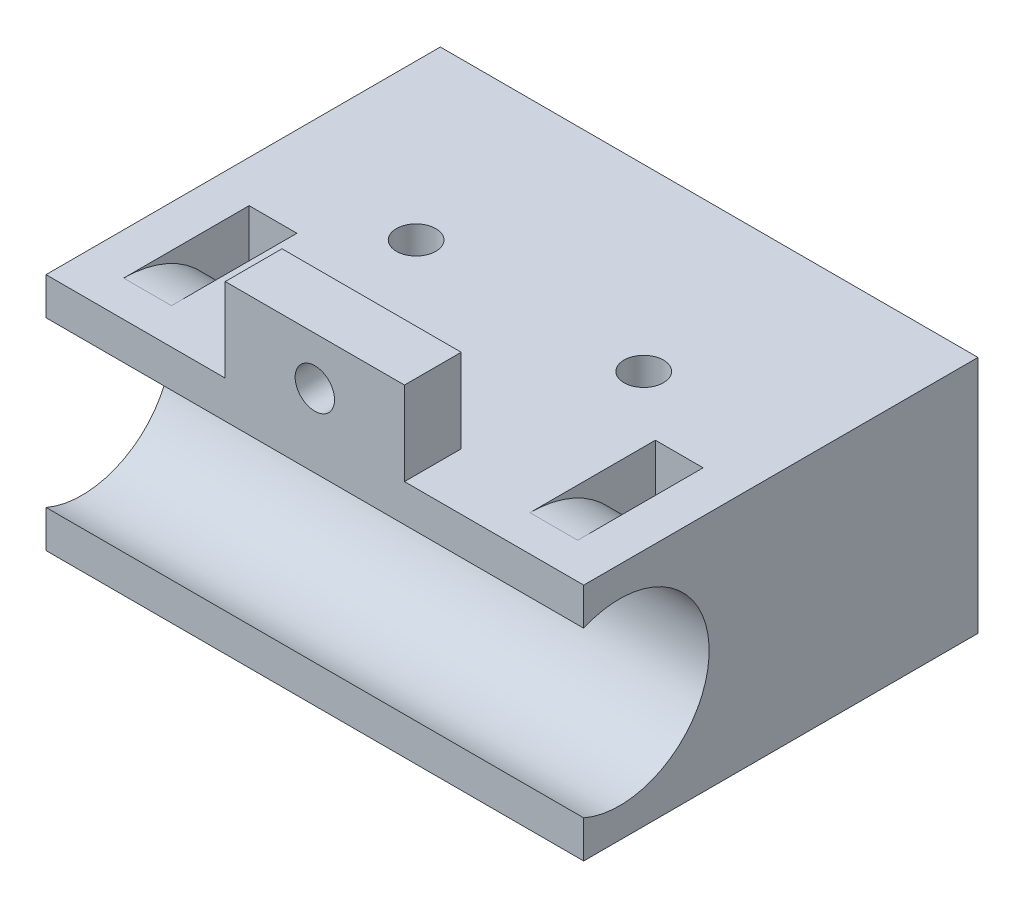
SolidWorks part; units mm, degrees
ref_plane "Front Plane" through (0, 0, 0) normal (0, 0, 1) x (1, 0, 0)
ref_plane "Top Plane" through (0, 0, 0) normal (0, 1, 0) x (1, 0, 0)
ref_plane "Right Plane" through (0, 0, 0) normal (1, 0, 0) x (0, 0, -1)
sketch "Sketch2" plane through (0, 0, 0) normal (0, 0, 1) x (1, 0, 0)
  line L1 (22.5, 10) -> (-22.5, 10)
  line L2 (22.5, 10) -> (22.5, -10)
  line L3 (22.5, -10) -> (-22.5, -10)
  line L4 (-22.5, 10) -> (-22.5, -10)
  line L5 (22.5, 10) -> (-22.5, -10) construction
  line L6 (22.5, -10) -> (-22.5, 10) construction
  point P0 (0, 0)
  dimension "D1" = 20
  dimension "D2" = 45
extrude "Boss-Extrude1" add sketch "Sketch2" along normal blind 33
hole_wizard "M4x0.7 Tapped Hole1" positions "Sketch7" profile "Sketch6" tap size "M4x0.7" standard "ANSI Metric" end condition through all
sketch "Sketch7" plane through (0, -10, 0) normal (0, -1, 0) x (-1, 0, 0)
  line L0 (0, 0) -> (0, -15) construction
  line L3 (9.525, -15) -> (-9.525, -15) construction
  point P0 (-9.525, -15)
  point P2 (9.525, -15)
  dimension "D1" = 19.05
  dimension "D2" = 15
cosmetic thread "Hole Thread1" parameters "D2"=4
cosmetic thread "Hole Thread2" parameters "D2"=4
sketch "Sketch6" plane through (9.525, -10, 15) normal (1, 0, 0) x (0, 0, -1)
  line L0 (0, 0) -> (0, 20)
  line L1 (0, 20) -> (1.65, 20)
  line L2 (1.65, 20) -> (1.65, 0)
  line L5 (1.65, 0) -> (0, 0)
  line L11 (0, -6.35) -> (0, 107.95) construction
  dimension "Thru Tap Drill Dia." = 3.3
  dimension "Thru Tap Drill Depth" = 20
sketch "Sketch3" plane through (22.5, 0, 0) normal (1, 0, 0) x (0, 0, -1)
  line L0 (-30, 0) -> (0, 0) construction
  circle A0 centre (-30, 0) radius 7.5
  dimension "D1" = 15
  dimension "D2" = 30
extrude "Cut-Extrude1" cut sketch "Sketch3" against normal blind 45
sketch "Sketch4" plane through (0, 0, 0) normal (0, 0, -1) x (-1, 0, 0)
  line L4 (22.5, -10) -> (22.5, 10)
  line L5 (22.5, 10) -> (-22.5, 10)
  line L6 (-22.5, 10) -> (-22.5, -10)
  line L7 (-22.5, -10) -> (22.5, -10)
  line L8 (22.5, -10) -> (22.5, 10)
  line L9 (22.5, 10) -> (-22.5, 10)
  line L10 (-22.5, 10) -> (-22.5, -10)
  line L11 (-22.5, -10) -> (22.5, -10)
  circle A0 centre (-15, 0) radius 4
  circle A1 centre (15, 0) radius 4
  dimension "D2" = 8
  dimension "D3" = 30
  dimension "D4" = 15
  dimension "D1" = 0
extrude "Cut-Extrude2" cut sketch "Sketch4" against normal blind 10 contours A0 | A1 region at (15, 0, 0) region at (-15, 0, 0)
hole_wizard "M3x0.5 Tapped Hole1" positions "Sketch15" profile "Sketch16" tap size "M3x0.5" standard "ANSI Metric"
sketch "Sketch15" plane through (0, 10, 0) normal (0, 1, 0) x (1, 0, 0)
  line L0 (0, 0) -> (0, -5) construction
  line L3 (-9.525, -5) -> (9.525, -5) construction
  point P0 (9.525, -5)
  point P2 (-9.525, -5)
  dimension "D1" = 19.05
  dimension "D2" = 5
sketch "Sketch16" plane through (9.525, 10, 5) normal (1, 0, 0) x (0, 0, 1)
  line L0 (0, 0) -> (0, 9.2511)
  line L1 (0, 9.2511) -> (1.25, 8.5)
  line L2 (1.25, 8.5) -> (1.25, 0)
  line L5 (1.25, 0) -> (0, 0)
  line L10 (0, 9.2511) -> (-1.25, 8.5) construction
  line L11 (0, -6.35) -> (0, 107.95) construction
  dimension "Tap Drill Dia." = 2.5
  dimension "Tap Drill Depth" = 8.5
  dimension "Drill Angle" = 118
cosmetic thread "Hole Thread7" parameters "D1"=6, "D2"=3
cosmetic thread "Hole Thread8" parameters "D1"=6, "D2"=3
sketch "Sketch5" plane through (0, -10, 0) normal (0, -1, 0) x (1, 0, 0)
  line L0 (0, 19.5) -> (0, 0) construction
  line L1 (-19, 21) -> (-15, 21)
  line L2 (-19, 21) -> (-19, 19.5)
  line L3 (-19, 19.5) -> (-15, 19.5)
  line L4 (-15, 21) -> (-15, 19.5)
  line L5 (-2, 19.5) -> (2, 19.5)
  line L6 (-2, 19.5) -> (-2, 21)
  line L7 (-2, 21) -> (2, 21)
  line L8 (2, 19.5) -> (2, 21)
  line L9 (15, 19.5) -> (19, 19.5)
  line L10 (15, 19.5) -> (15, 21)
  line L11 (15, 21) -> (19, 21)
  line L12 (19, 19.5) -> (19, 21)
  line L13 (-22.5, 19.5) -> (-19, 19.5) construction
  line L14 (-22.5, 33) -> (-22.5, 0) construction
  line L15 (-2, 19.5) -> (-15, 19.5) construction
  line L16 (2, 19.5) -> (15, 19.5) construction
  line L17 (19, 19.5) -> (22.5, 19.5) construction
  line L18 (22.5, 33) -> (22.5, 0) construction
  line L27 (-22.5, 0) -> (22.5, 0) construction
  dimension "D1" = 4
  dimension "D2" = 1.5
  dimension "D3" = 30
  dimension "D4" = 21
extrude "Cut-Extrude3" cut sketch "Sketch5" against normal blind 39 contours L4 L1 L2 L3 | L9 L12 L11 L10 region at (-17, -10, 20.25) region at (17, -10, 20.25)
fillet "Fillet1" radius 9 2 edges at (17, -10, 21) (-17, -10, 21)
sketch "Sketch8" plane through (0, -10, 0) normal (0, -1, 0) x (1, 0, 0)
  line L1 (-7.5, 28.25) -> (7.5, 28.25)
  line L2 (-7.5, 28.25) -> (-7.5, 33)
  line L3 (-7.5, 33) -> (7.5, 33)
  line L4 (-22.5, 33) -> (22.5, 33) construction
  line L5 (0, 28.25) -> (0, 0) construction
  line L8 (7.5, 28.25) -> (7.5, 33)
  dimension "D1" = 4.75
  dimension "D2" = 15
extrude "Boss-Extrude2" add sketch "Sketch8" along normal blind 7
hole_wizard "M4x0.7 Tapped Hole3" positions "Sketch19" profile "Sketch20" tap size "M4x0.7" standard "ANSI Metric" end condition through all
sketch "Sketch19" plane through (0, 0, 28.25) normal (0, 0, -1) x (-1, 0, 0)
  line L0 (7.5, -10) -> (-7.5, -10) construction
  point P0 (0, -13)
  point P5 (0, 0)
  point P6 (0, 0)
  dimension "D1" = 3
sketch "Sketch20" plane through (0, -13, 28.25) normal (1, 0, 0) x (0, 1, 0)
  line L0 (0, 0) -> (0, 4.75)
  line L1 (0, 4.75) -> (1.65, 4.75)
  line L2 (1.65, 4.75) -> (1.65, 0)
  line L5 (1.65, 0) -> (0, 0)
  line L11 (0, -6.35) -> (0, 107.95) construction
  dimension "Thru Tap Drill Dia." = 3.3
  dimension "Thru Tap Drill Depth" = 4.75
cosmetic thread "Hole Thread6" parameters "D2"=4
move or copy body "Body-Move/Copy1" bodies to move or copy 117 copy no rotation origin (0, -3.5, 0) rotation axis (0, 0, 1) rotation angle 180
